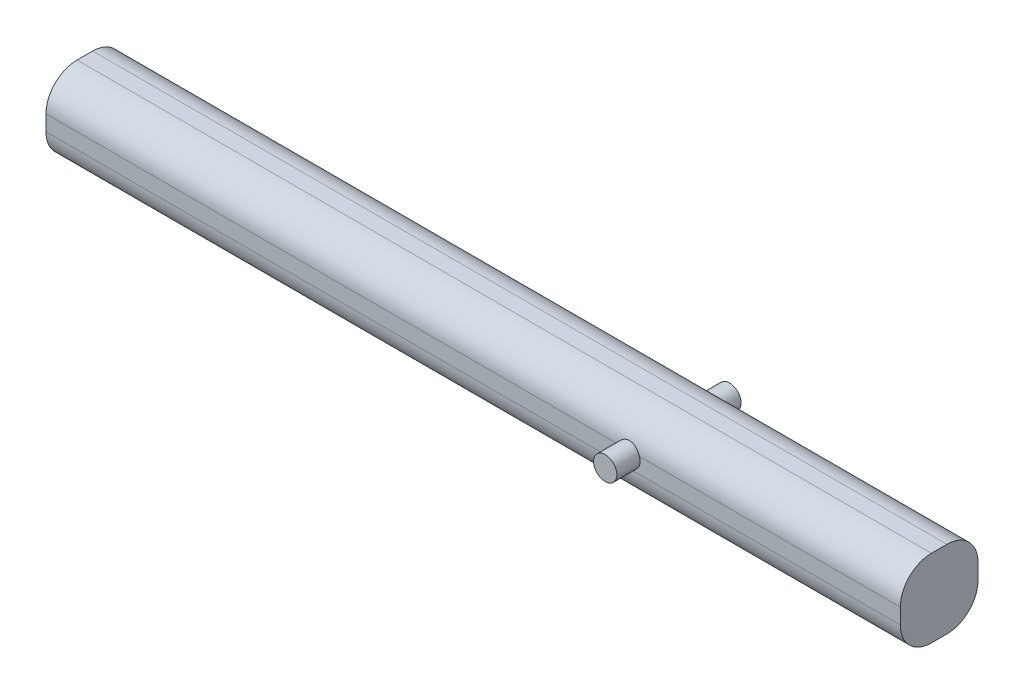
SolidWorks part; units mm, degrees
ref_plane "Front Plane" through (0, 0, 0) normal (0, 0, 1) x (1, 0, 0)
ref_plane "Top Plane" through (0, 0, 0) normal (0, 1, 0) x (1, 0, 0)
ref_plane "Right Plane" through (0, 0, 0) normal (1, 0, 0) x (0, 0, -1)
sketch "Sketch1" plane through (0, 0, 0) normal (0, 0, 1) x (1, 0, 0)
  line L1 (-2320.0326, 1186.8893) -> (3179.9674, 1186.8893)
  line L2 (-2320.0326, 1186.8893) -> (-2320.0326, 686.8893)
  line L3 (-2320.0326, 686.8893) -> (3179.9674, 686.8893)
  line L4 (3179.9674, 1186.8893) -> (3179.9674, 686.8893)
  dimension "D1" = 5500
  dimension "D2" = 500
extrude "Boss-Extrude1" add sketch "Sketch1" along normal blind 500
fillet "Fillet1" radius 200 4 edges at (429.9674, 686.8893, 0) (429.9674, 686.8893, 500) (429.9674, 1186.8893, 0) (429.9674, 1186.8893, 500)
sketch "Sketch2" plane through (-2320.0326, 0, 0) normal (-1, 0, 0) x (0, 0, 1)
  line L0 (300, 686.8893) -> (200, 686.8893) construction
  line L2 (0, 986.8893) -> (0, 886.8893) construction
  circle A0 centre (255, 941.8893) radius 210
  dimension "D1" = 255
  dimension "D2" = 255
extrude "Cut-Extrude1" cut sketch "Sketch2" against normal blind 5499
sketch "Sketch3" plane through (0, 0, 500) normal (0, 0, 1) x (1, 0, 0)
  line L0 (3179.9674, 886.8893) -> (3179.9674, 986.8893) construction
  line L1 (-2320.0326, 1186.8893) -> (3179.9674, 1186.8893) construction
  circle A0 centre (1429.9674, 961.8893) radius 75
  dimension "D2" = 150
  dimension "D3" = 225
  dimension "D1" = 1750
extrude "Boss-Extrude2" add sketch "Sketch3" along normal blind 150 and the other way blind 650
sketch "Sketch4" plane through (-2320.0326, 0, 0) normal (-1, 0, 0) x (0, 0, 1)
  circle A0 centre (255, 941.8893) radius 210
extrude "Cut-Extrude2" cut sketch "Sketch4" against normal blind 5499
